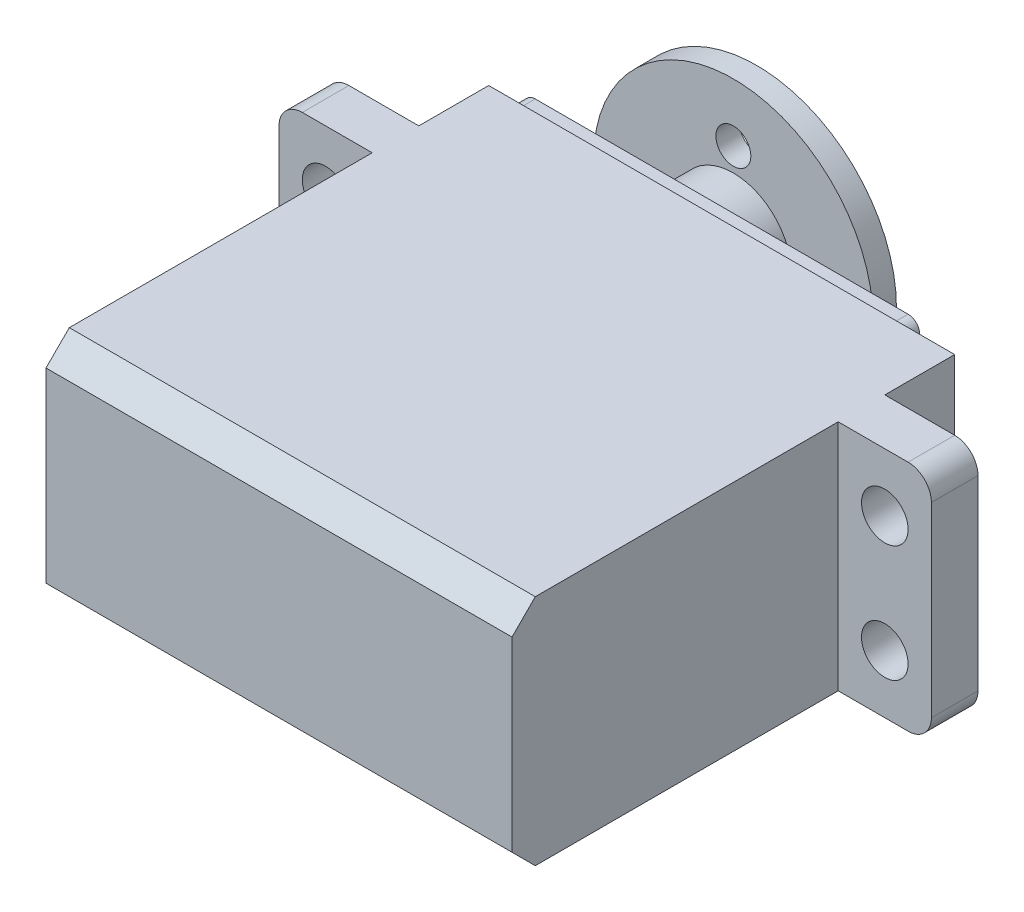
SolidWorks part; units mm, degrees
ref_plane "前视基准面" through (0, 0, 0) normal (0, 0, 1) x (1, 0, 0)
ref_plane "上视基准面" through (0, 0, 0) normal (0, 1, 0) x (1, 0, 0)
ref_plane "右视基准面" through (0, 0, 0) normal (1, 0, 0) x (0, 0, -1)
sketch "草图1" plane through (0, 0, 0) normal (0, 1, 0) x (1, 0, 0)
  line L1 (-20, 20) -> (20, 20)
  line L2 (-20, 20) -> (-20, -20)
  line L3 (-20, -20) -> (20, -20)
  line L4 (20, 20) -> (20, -20)
  line L5 (-20, 20) -> (20, -20) construction
  line L6 (-20, -20) -> (20, 20) construction
  point P0 (0, 0)
  dimension "D1" = 40
  dimension "D2" = 40
extrude "凸台-拉伸1" add sketch "草图1" along normal blind 20
fillet "倒角1" radius 2 1 edges at (0, 0, 20) type face fillet profile chamfer first side face at (0, 0, 0) second side face at (0, 10, 20)
fillet "倒角2" radius 2 1 edges at (0, 20, 20) type face fillet profile chamfer first side face at (0, 20, 0) second side face at (0, 11, 20)
sketch "草图2" plane through (0, 0, -20) normal (0, 0, -1) x (-1, 0, 0)
  line L1 (-20, 20) -> (20, 20)
  line L2 (-20, 20) -> (-20, 0)
  line L3 (-20, 0) -> (20, 0)
  line L4 (20, 20) -> (20, 0)
  line L7 (19, 1) -> (-15, 1)
  line L8 (19, 1) -> (19, 19)
  line L9 (19, 19) -> (-15, 19)
  line L10 (-15, 1) -> (-15, 19)
  point P0 (0, 10)
  point P6 (2, 10)
  dimension "D1" = 40
  dimension "D2" = 20
  dimension "D3" = 5
  dimension "D4" = 1
  dimension "D5" = 1
  dimension "D6" = 1
extrude "切除-拉伸1" cut sketch "草图2" against normal blind 2
fillet "圆角1" radius 1 1 edges at (15, 1, -19) type face fillet first side face at (15, 10, -19) second side face at (-2, 1, -19)
fillet "圆角2" radius 1 1 edges at (15, 19, -19) type face fillet first side face at (15, 10.5, -19) second side face at (-2, 19, -19)
fillet "圆角3" radius 1 1 edges at (-19, 1, -19) type face fillet first side face at (-19, 10, -19) second side face at (-2.5, 1, -19)
fillet "圆角4" radius 1 1 edges at (-19, 19, -19) type face fillet first side face at (-19, 10.5, -19) second side face at (-2.5, 19, -19)
sketch "草图3" plane through (0, 0, -20) normal (0, 0, -1) x (-1, 0, 0)
  line L0 (20, 0) -> (20, 20) construction
  line L5 (-14, 1) -> (18, 1) construction
  circle A0 centre (8, 10) radius 5
  dimension "D3" = 10
  dimension "D1" = 12
  dimension "D2" = 9
extrude "凸台-拉伸2" add sketch "草图3" along normal blind 7
sketch "草图4" plane through (0, 0, -27) normal (0, 0, -1) x (-1, 0, 0)
  circle A0 centre (8, 10) radius 12
  dimension "D1" = 24
extrude "凸台-拉伸3" add sketch "草图4" along normal blind 2
sketch "草图5" plane through (0, 0, -29) normal (0, 0, -1) x (-1, 0, 0)
  circle A2 centre (8, 17) radius 1.5
  circle A3 centre (15, 10) radius 1.5
  circle A4 centre (8, 3) radius 1.5
  circle A5 centre (1, 10) radius 1.5
  dimension "D1" = 3
  dimension "D3" = 4
extrude "切除-拉伸2" cut sketch "草图5" against normal up to next
sketch "草图6" plane through (-20, 0, 0) normal (-1, 0, 0) x (0, 0, 1)
  line L0 (-18, 20) -> (18, 20) construction
  line L1 (-12, 20) -> (-8, 20)
  line L2 (-12, 20) -> (-12, 0)
  line L3 (-12, 0) -> (-8, 0)
  line L4 (-8, 20) -> (-8, 0)
  line L5 (-18, 0) -> (18, 0) construction
  line L6 (20, 18) -> (20, 2) construction
  dimension "D1" = 28
  dimension "D2" = 4
extrude "凸台-拉伸4" add sketch "草图6" along normal blind 8
sketch "草图7" plane through (0, 0, -12) normal (0, 0, -1) x (-1, 0, 0)
  circle A0 centre (24, 15) radius 2
  circle A1 centre (24, 5) radius 2
  point P12 (46.9123, -5.4457)
  dimension "D1" = 4
  dimension "D2" = 4
  dimension "D5" = 10
extrude "切除-拉伸3" cut sketch "草图7" against normal up to next
fillet "圆角5" radius 2 1 edges at (-28, 20, -10) type face fillet first side face at (-12, 20, -5) second side face at (-28, 10, -10)
fillet "圆角6" radius 2 1 edges at (-28, 0, -10) type face fillet first side face at (-28, 9, -10) second side face at (-12, 0, -5)
mirror "镜向1" about plane through (0, 0, 0) normal (1, 0, 0) of "圆角6", "圆角5", "切除-拉伸3", "凸台-拉伸4"
